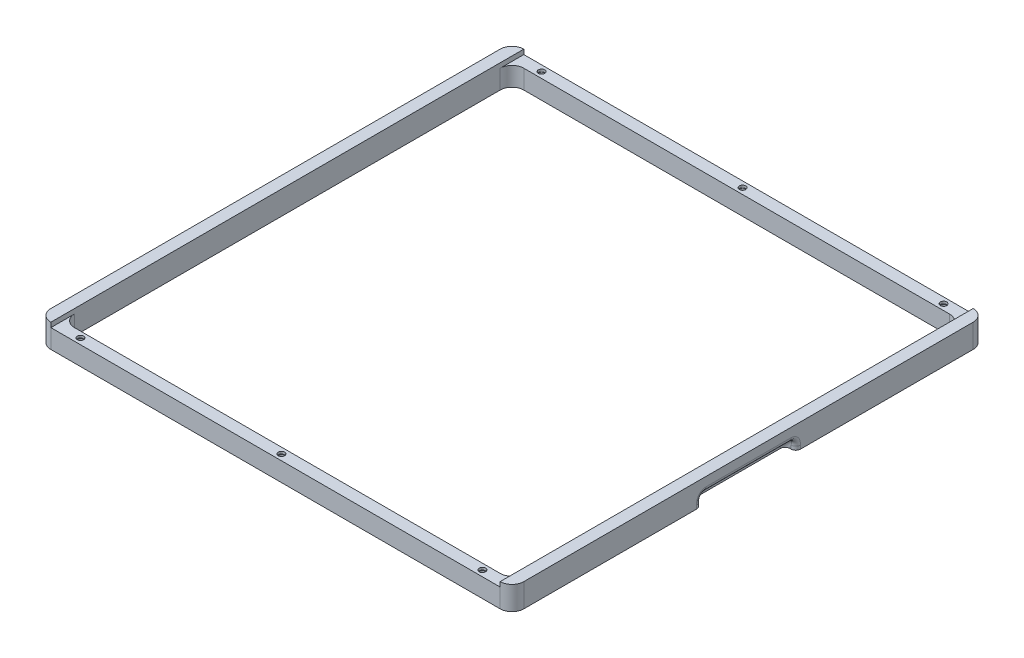
SolidWorks part; units mm, degrees
ref_plane "前视基准面" through (0, 0, 0) normal (0, 0, 1) x (1, 0, 0)
ref_plane "上视基准面" through (0, 0, 0) normal (0, 1, 0) x (1, 0, 0)
ref_plane "右视基准面" through (0, 0, 0) normal (1, 0, 0) x (0, 0, -1)
other "Configuration Table"
sketch "草图1" plane through (0, 0, 0) normal (0, 1, 0) x (1, 0, 0)
  line L1 (-446.8557, 175.2524) -> (-246.8557, 175.2524)
  line L2 (-446.8557, 175.2524) -> (-446.8557, -24.7476)
  line L3 (-446.8557, -24.7476) -> (-246.8557, -24.7476)
  line L4 (-246.8557, 175.2524) -> (-246.8557, -24.7476)
  dimension "D1" = 200
  dimension "D2" = 200
extrude "凸台-拉伸1" add sketch "草图1" along normal blind 10
fillet "圆角1" radius 5 4 edges at (-246.8557, 5, -175.2524) (-446.8557, 5, -175.2524) (-246.8557, 5, 24.7476) (-446.8557, 5, 24.7476)
ref_plane "基准面1" through (0, 0, -25.7524) normal (0, 0, 1) x (1, 0, 0)
sketch "草图4" plane through (0, 0, 0) normal (0, -1, 0) x (1, 0, 0)
  line L0 (-251.8557, -175.2524) -> (-441.8557, -175.2524) construction
  line L1 (-251.8557, -170.2524) -> (-441.8557, -170.2524)
  line L2 (-251.8557, -170.2524) -> (-251.8557, 19.7476)
  line L3 (-251.8557, 19.7476) -> (-441.8557, 19.7476)
  line L4 (-441.8557, -170.2524) -> (-441.8557, 19.7476)
  line L5 (-446.8557, -170.2524) -> (-446.8557, 19.7476) construction
  dimension "D1" = 190
  dimension "D2" = 190
  dimension "D3" = 5
  dimension "D4" = 5
extrude "切除-拉伸1" cut sketch "草图4" against normal blind 8
fillet "圆角2" radius 5 4 edges at (-251.8557, 4, -170.2524) (-251.8557, 4, 19.7476) (-441.8557, 4, 19.7476) (-441.8557, 4, -170.2524)
ref_plane "基准面2" through (0, 0, -75.2524) normal (0, 0, 1) x (1, 0, 0)
sketch "草图5" plane through (0, 0, -75.2524) normal (0, 0, 1) x (1, 0, 0)
  circle A0 centre (-246.8557, 0) radius 4.5
  dimension "D1" = 9
extrude "切除-拉伸2" cut sketch "草图5" against normal mid plane 40
fillet "圆角3" radius 2 5 edges at (-246.8557, 2.25, -55.2524) (-250.0376, 3.182, -95.2524) (-246.8557, 2.25, -95.2524) (-246.8557, 4.5, -75.2524) (-250.0376, 3.182, -55.2524)
ref_plane "基准面3" through (0, 1, 0) normal (0, -1, 0) x (-1, 0, 0)
sketch "草图6" plane through (0, 1, 0) normal (0, -1, 0) x (-1, 0, 0)
  line L0 (246.8557, -19.7476) -> (246.8557, 53.2524) construction
  line L1 (441.8557, -24.7476) -> (251.8557, -24.7476) construction
  circle A0 centre (250.8557, -20.7476) radius 2.1
  dimension "D1" = 4.2
  dimension "D2" = 4
  dimension "D3" = 4
extrude "切除-拉伸3" cut sketch "草图6" against normal blind 5.1
mirror "镜向1" about plane through (0, 0, -75.2524) normal (0, 0, 1) of "切除-拉伸3"
sketch "草图7" plane through (0, 0, 24.7476) normal (0, 0, 1) x (1, 0, 0)
sketch "草图8" plane through (0, 0, 24.7476) normal (0, 0, 1) x (1, 0, 0)
  line L0 (-251.8557, 0) -> (-251.8557, 10) construction
  line L1 (-441.8557, 10) -> (-251.8557, 10)
  line L2 (-441.8557, 10) -> (-441.8557, 8)
  line L3 (-441.8557, 8) -> (-251.8557, 8)
  line L4 (-251.8557, 10) -> (-251.8557, 8)
  dimension "D1" = 2
extrude "切除-拉伸4" cut sketch "草图8" against normal through all
sketch "草图9" plane through (0, 8, 0) normal (0, 1, 0) x (1, 0, 0)
  line L0 (-441.8557, 175.2524) -> (-441.8557, -24.7476) construction
  line L1 (-256.8557, -19.7476) -> (-436.8557, -19.7476) construction
  circle A0 centre (-431.8557, -22.2476) radius 1.35
  circle A1 centre (-431.8557, -22.2476) radius 1.15
  dimension "D1" = 2.7
  dimension "D2" = 10
  dimension "D4" = 2.3
  dimension "D3" = 2.5
extrude "切除-拉伸5" cut sketch "草图9" against normal blind 3.1 contours A1
extrude "切除-拉伸6" cut sketch "草图9<3>" against normal blind 1
sketch "草图9<3>" plane through (0, 8, 0) normal (0, 1, 0) x (1, 0, 0) same geometry as "草图9"
pattern_linear "阵列(线性)2" count 2 spacing 195 along (0, 0, -1) count 3 spacing 85 along (1, 0, 0) of "切除-拉伸6", "切除-拉伸5"
sketch "草图10" plane through (-446.8557, 0, 0) normal (-1, 0, 0) x (0, 0, 1)
  line L0 (-170.2524, 0) -> (19.7476, 0) construction
  line L1 (-160.2524, 0) -> (-146.2524, 0)
  line L2 (-160.2524, 0) -> (-160.2524, 7)
  line L3 (-160.2524, 7) -> (-146.2524, 7)
  line L4 (-146.2524, 0) -> (-146.2524, 7)
  line L5 (-170.2524, 10) -> (-170.2524, 0) construction
  line L8 (-160.2524, 0) -> (-146.2524, 0)
  line L9 (-160.2524, 0) -> (-160.2524, 1.2)
  line L10 (-160.2524, 1.2) -> (-146.2524, 1.2)
  line L11 (-146.2524, 0) -> (-146.2524, 1.2)
  circle A0 centre (-156.5024, 3.75) radius 1.15
  circle A1 centre (-156.5024, 3.75) radius 1.35
  circle A2 centre (-150.0024, 3.75) radius 1.15
  circle A3 centre (-150.0024, 3.75) radius 1.35
  line M5 (-170.2524, 0) -> (19.7476, 0)
  dimension "D4" = 2.3
  dimension "D5" = 2.7
  dimension "D6" = 2.3
  dimension "D7" = 2.7
  dimension "D1" = 14
  dimension "D2" = 7
  dimension "D3" = 10
  dimension "D8" = 6.5
  dimension "D9" = 3.75
  dimension "D10" = 3.75
  dimension "D11" = 3.75
  dimension "D12" = 1.2
extrude "切除-拉伸7" cut sketch "草图10" against normal blind 2 contours A1 A0 | A3 A2 | L10 L2 L4 M5 region at (-446.8557, 0.6, -153.2524) region at (-446.8557, 3.75, -157.8142) region at (-446.8557, 3.75, -151.3142)
extrude "切除-拉伸8" cut sketch "草图10<3>" against normal blind 1 contours L2 L10 L4 L3 A3 A1 region at (-446.8557, 4.1575, -153.2524)
sketch "草图10<3>" plane through (-446.8557, 0, 0) normal (-1, 0, 0) x (0, 0, 1) same geometry as "草图10"
extrude "切除-拉伸9" cut sketch "草图10<4>" against normal blind 4 contours A0 | A2 region at (-446.8557, 3.75, -156.5024) region at (-446.8557, 3.75, -150.0024)
sketch "草图10<4>" plane through (-446.8557, 0, 0) normal (-1, 0, 0) x (0, 0, 1) same geometry as "草图10"
pattern_linear "阵列(线性)3" count 3 spacing 78 along (0, 0, 1) of "切除-拉伸8", "切除-拉伸7", "切除-拉伸9"
